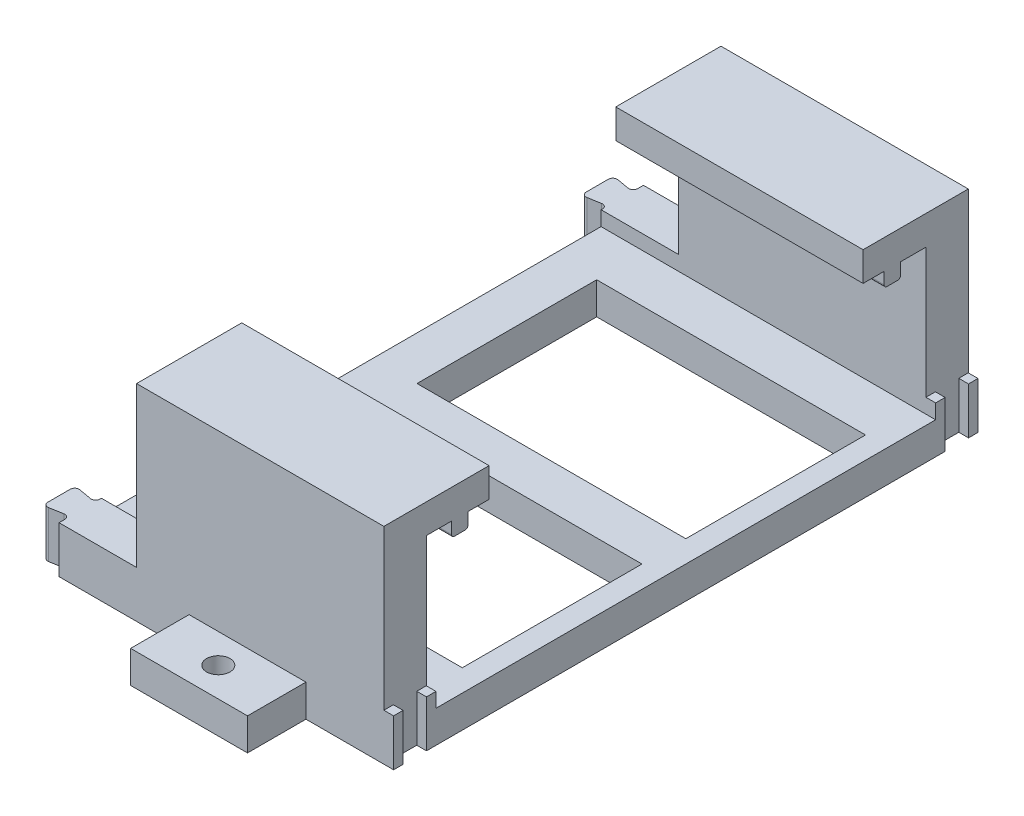
SolidWorks part; units mm, degrees
ref_plane "Front Plane" through (0, 0, 0) normal (0, 0, 1) x (1, 0, 0)
ref_plane "Top Plane" through (0, 0, 0) normal (0, 1, 0) x (1, 0, 0)
ref_plane "Right Plane" through (0, 0, 0) normal (1, 0, 0) x (0, 0, -1)
sketch "Sketch1" plane through (0, 0, 0) normal (0, 1, 0) x (1, 0, 0)
  line L1 (-184.5, -100) -> (184.5, -100)
  line L2 (-184.5, -100) -> (-184.5, 100)
  line L3 (-184.5, 100) -> (184.5, 100)
  line L4 (184.5, -100) -> (184.5, 100)
  line L5 (-184.5, -100) -> (184.5, 100) construction
  line L6 (-184.5, 100) -> (184.5, -100) construction
  point P0 (0, 0)
  dimension "D1" = 200
  dimension "353" = 369
extrude "Boss-Extrude1" add sketch "Sketch1" along normal blind 16
sketch "Sketch2" plane through (0, 16, 0) normal (0, 1, 0) x (1, 0, 0)
  line L0 (-184.5, -100) -> (184.5, -100) construction
  line L1 (-184.5, -100) -> (-155.6166, -100)
  line L2 (-184.5, -100) -> (-184.5, -36.5)
  line L3 (-184.5, -36.5) -> (-169.5, -36.5)
  line L4 (-169.5, -84) -> (-169.5, -36.5)
  line L5 (-184.5, 100) -> (-155.6166, 100)
  line L6 (-184.5, 100) -> (-184.5, 36.5)
  line L7 (-184.5, 36.5) -> (-169.5, 36.5)
  line L8 (-169.5, 84) -> (-169.5, 36.5)
  line L9 (-155.6166, 100) -> (-119.5, 100)
  line L11 (-169.5, 84) -> (-119.5, 84)
  line L12 (-119.5, 100) -> (-119.5, 84)
  line L13 (-155.6166, -100) -> (-119.5, -100)
  line L15 (-169.5, -84) -> (-119.5, -84)
  line L16 (-119.5, -100) -> (-119.5, -84)
  line L17 (-44.5, -100) -> (84.5, -100)
  line L18 (-44.5, -100) -> (-44.5, -84)
  line L19 (-44.5, -84) -> (84.5, -84)
  line L20 (84.5, -100) -> (84.5, -84)
  line L22 (-44.5, 100) -> (84.5, 100)
  line L23 (-44.5, 100) -> (-44.5, 84)
  line L24 (-44.5, 84) -> (84.5, 84)
  line L25 (84.5, 100) -> (84.5, 84)
  line L26 (184.5, -100) -> (184.5, 100) construction
  line L27 (184.5, 100) -> (-184.5, 100) construction
  point P28 (84.5, -92)
  dimension "D1" = 65
  dimension "D2" = 15
  dimension "D3" = 65
  dimension "D4" = 15
  dimension "D5" = 16
  dimension "D6" = 50
  dimension "D7" = 50
  dimension "D8" = 16
  dimension "D9" = 75
  dimension "D10" = 100
extrude "Boss-Extrude2" add sketch "Sketch2" along normal blind 12
sketch "Sketch3" plane through (0, 16, 0) normal (0, 1, 0) x (1, 0, 0)
  line L0 (-119.5, -84) -> (-169.5, -84) construction
  line L1 (-169.5, 84) -> (172.5, 84)
  line L2 (-169.5, 84) -> (-169.5, -84)
  line L3 (-169.5, -84) -> (172.5, -84)
  line L4 (172.5, 84) -> (172.5, -84)
  dimension "D1" = 342
extrude "Cut-Extrude1" cut sketch "Sketch3" against normal blind 5
sketch "Sketch4" plane through (0, 0, -100) normal (0, 0, -1) x (-1, 0, 0)
  line L0 (-84.5, 28) -> (44.5, 28) construction
  line L1 (-69.5, 16) -> (30.5, 16)
  line L2 (-69.5, 16) -> (-69.5, 28)
  line L3 (-69.5, 28) -> (30.5, 28)
  line L4 (30.5, 16) -> (30.5, 28)
  line L5 (-69.5, 16) -> (30.5, 28) construction
  line L6 (-69.5, 28) -> (30.5, 16) construction
  line L8 (-84.5, 28) -> (-84.5, 16) construction
  point P0 (-19.5, 22)
  dimension "D1" = 100
  dimension "D2" = 15
extrude "Boss-Extrude3" add sketch "Sketch4" along normal blind 60
sketch "Sketch8" plane through (0, 28, 0) normal (0, 1, 0) x (1, 0, 0)
  line L0 (-184.5, 36.5) -> (-169.5, 36.5)
  line L1 (-169.5, 36.5) -> (-169.5, 84)
  line L2 (-169.5, 84) -> (-119.5, 84)
  line L3 (-119.5, 84) -> (-119.5, 100)
  line L4 (-119.5, 100) -> (-184.5, 100)
  line L5 (-184.5, 100) -> (-184.5, 36.5)
extrude "Boss-Extrude5" add sketch "Sketch8" along normal blind 42
sketch "Sketch9" plane through (0, 70, 0) normal (0, 1, 0) x (1, 0, 0)
  line L0 (-119.5, 84) -> (-119.5, 70)
  line L1 (-119.5, 70) -> (-155.5, 70)
  line L2 (-155.5, 70) -> (-155.5, 35)
  line L3 (-155.5, 35) -> (-169.5, 35)
  line L4 (-169.5, 36.5) -> (-169.5, 84) construction
  line L5 (-169.5, 84) -> (-169.5, -84) construction
  line L6 (172.5, 84) -> (-169.5, 84) construction
  dimension "D1" = 14
  dimension "D2" = 14
extrude "Extrude-Thin1" add sketch "Sketch9" against normal blind 7 thin thin type one direction wall 10
sketch "Sketch11" plane through (0, 70, 0) normal (0, 1, 0) x (1, 0, 0)
  line L1 (-184.5, 100) -> (-44.5, 100)
  line L2 (-184.5, 100) -> (-184.5, -100)
  line L3 (-184.5, -100) -> (-44.5, -100)
  line L4 (-44.5, 100) -> (-44.5, -100)
extrude "Cut-Extrude5" cut sketch "Sketch11" against normal through all
sketch "Sketch13" plane through (0, 28, 0) normal (0, 1, 0) x (1, 0, 0)
  line L0 (-44.5, 96.22) -> (-44.5, 87.78)
  line L1 (-44.5, 100) -> (-44.5, 84) construction
  line L2 (-44.5, 87.78) -> (-52.3, 86.4046)
  line L3 (-52.3, 86.4046) -> (-52.3, 97.5954)
  line L4 (-52.3, 97.5954) -> (-44.5, 96.22)
  line L5 (-44.5, -87.78) -> (-44.5, -96.22)
  line L6 (-44.5, -96.22) -> (-52.5, -97.6306)
  line L7 (-52.5, -97.6306) -> (-52.5, -86.3694)
  line L8 (-52.5, -86.3694) -> (-44.5, -87.78)
  line L9 (-44.5, -84) -> (-44.5, -100) construction
  dimension "D1" = 3.78
  dimension "D2" = 3.78
  dimension "D3" = 7.8
  dimension "D4" = 80
  dimension "D5" = 80
  dimension "D6" = 3.78
  dimension "D7" = 3.78
  dimension "D8" = 80
  dimension "D9" = 8
  dimension "D10" = 80
extrude "Boss-Extrude6" add sketch "Sketch13" against normal through all
fillet "Fillet1" radius 1.5 8 edges at (-44.5, 14, 87.78) (-52.5, 14, 86.3694) (-52.5, 14, 97.6306) (-44.5, 14, 96.22) (-44.5, 14, -96.22) (-44.5, 14, -87.78) (-52.3, 14, -86.4046) (-52.3, 14, -97.5954)
sketch "Sketch14" plane through (0, 0, 0) normal (0, 0, 1) x (1, 0, 0)
  line L0 (84.5, 16) -> (184.5, 16) construction
  line L1 (84.5, 28) -> (-67.1004, 28)
  line L2 (84.5, 28) -> (84.5, 16)
  line L3 (84.5, 16) -> (-67.1004, 16)
  line L4 (-67.1004, 28) -> (-67.1004, 16)
extrude "Cut-Extrude6" cut sketch "Sketch14" along normal through all and the other way through all
sketch "Sketch15" plane through (0, 16, 0) normal (0, 1, 0) x (1, 0, 0)
  line L0 (184.5, 100) -> (-44.5, 100) construction
  line L1 (-17.9669, 100) -> (79.8991, 100)
  line L2 (-17.9669, 100) -> (-17.9669, 84)
  line L3 (-17.9669, 84) -> (79.8991, 84)
  line L4 (79.8991, 100) -> (79.8991, 84)
  line L5 (172.5, 84) -> (-44.5, 84) construction
extrude "Boss-Extrude7" add sketch "Sketch15" along normal blind 62
sketch "Sketch16" plane through (0, 0, -84) normal (0, 0, 1) x (1, 0, 0)
  line L0 (79.8991, 78) -> (79.8991, 16) construction
  line L1 (-17.9669, 78) -> (79.8991, 78)
  line L2 (-17.9669, 78) -> (-17.9669, 60.5)
  line L3 (-17.9669, 60.5) -> (79.8991, 60.5)
  line L4 (79.8991, 78) -> (79.8991, 60.5)
  line L5 (172.5, 11) -> (-44.5, 11) construction
  dimension "D1" = 49.5
extrude "Boss-Extrude8" add sketch "Sketch16" along normal blind 20
sketch "Sketch17" plane through (0, 60.5, 0) normal (0, -1, 0) x (1, 0, 0)
  line L0 (-17.9669, -64) -> (-17.9669, -84) construction
  line L1 (-17.9669, -71.2) -> (79.8991, -71.2)
  line L2 (-17.9669, -71.2) -> (-17.9669, -76.85)
  line L3 (-17.9669, -76.85) -> (79.8991, -76.85)
  line L4 (79.8991, -71.2) -> (79.8991, -76.85)
  line L5 (79.8991, -64) -> (79.8991, -84) construction
  line L6 (-17.9669, -84) -> (79.8991, -84) construction
  dimension "D1" = 5.65
  dimension "D2" = 7.15
extrude "Boss-Extrude9" add sketch "Sketch17" along normal blind 5
fillet "Fillet3" radius 1 2 edges at (30.9661, 55.5, -76.85) (30.9661, 55.5, -71.2)
sketch "Sketch18" plane through (0, 16, 0) normal (0, 1, 0) x (1, 0, 0)
  line L0 (184.5, -100) -> (184.5, 100) construction
  line L1 (172.5, 84) -> (184.5, 84)
  line L2 (172.5, 84) -> (172.5, -84)
  line L3 (172.5, -84) -> (184.5, -84)
  line L4 (184.5, 84) -> (184.5, -84)
  line L5 (-44.5, -84) -> (172.5, -84) construction
extrude "Cut-Extrude7" cut sketch "Sketch18" against normal blind 5
sketch "Sketch19" plane through (0, 0, -100) normal (0, 0, -1) x (-1, 0, 0)
  line L1 (0, 0) -> (-40, 0)
  line L2 (0, 0) -> (0, 11)
  line L3 (0, 11) -> (-40, 11)
  line L4 (-40, 0) -> (-40, 11)
  line L5 (-184.5, 0) -> (-144.5, 0)
  line L6 (-184.5, 0) -> (-184.5, 11)
  line L7 (-184.5, 11) -> (-144.5, 11)
  line L8 (-144.5, 0) -> (-144.5, 11)
  dimension "D1" = 11
  dimension "D2" = 11
  dimension "D3" = 40
  dimension "D4" = 40
extrude "Boss-Extrude10" add sketch "Sketch19" along normal blind 20
sketch "Sketch20" plane through (0, 11, 0) normal (0, 1, 0) x (1, 0, 0)
  line L0 (40, 120) -> (40, 100) construction
  line L1 (0, 120) -> (40, 120) construction
  line L2 (144.5, 120) -> (184.5, 120) construction
  line L3 (184.5, 120) -> (184.5, 100) construction
  circle A0 centre (164.5, 110) radius 4
  circle A1 centre (20, 110) radius 4
  dimension "D1" = 20
  dimension "D2" = 10
  dimension "D3" = 10
  dimension "D4" = 20
extrude "Cut-Extrude8" cut sketch "Sketch20" against normal through all
mirror "Mirror3" about plane through (0, 0, 0) normal (0, 0, 1) of "Cut-Extrude8", "Boss-Extrude10", "Boss-Extrude9", "Boss-Extrude7", "Boss-Extrude8", "Fillet3"
sketch "Sketch21" plane through (0, 11, 0) normal (0, 1, 0) x (1, 0, 0)
  line L1 (-29.5, 7.5) -> (62.5, 7.5)
  line L2 (-29.5, 7.5) -> (-29.5, 69)
  line L3 (-29.5, 69) -> (62.5, 69)
  line L4 (62.5, 7.5) -> (62.5, 69)
  line L5 (77.5, 69) -> (169.5, 69)
  line L6 (77.5, 69) -> (77.5, 7.5)
  line L7 (77.5, 7.5) -> (169.5, 7.5)
  line L8 (169.5, 69) -> (169.5, 7.5)
  line L9 (-44.5, -84) -> (-44.5, 84) construction
  line L10 (62.5, -7.5) -> (-29.5, -7.5)
  line L11 (62.5, -7.5) -> (62.5, -69)
  line L12 (62.5, -69) -> (-29.5, -69)
  line L13 (-29.5, -7.5) -> (-29.5, -69)
  line L14 (77.5, -7.5) -> (169.5, -7.5)
  line L15 (77.5, -7.5) -> (77.5, -69)
  line L16 (77.5, -69) -> (169.5, -69)
  line L17 (169.5, -7.5) -> (169.5, -69)
  line L18 (184.5, -84) -> (184.5, 84) construction
  line L19 (-44.5, -84) -> (184.5, -84) construction
  line L20 (184.5, 84) -> (79.8991, 84) construction
  line L21 (-17.9669, 84) -> (-44.5, 84) construction
  line L22 (-42.9, 0) -> (42.9, 0) construction
  dimension "D1" = 15
  dimension "D2" = 15
  dimension "D3" = 15
  dimension "D4" = 15
  dimension "D5" = 15
  dimension "D6" = 15
  dimension "D7" = 15
  dimension "D8" = 15
  dimension "D9" = 7.5
  dimension "D10" = 7.5
  dimension "D11" = 7.5
  dimension "D12" = 7.5
  dimension "D13" = 122
  dimension "D14" = 15
extrude "Cut-Extrude9" cut sketch "Sketch21" against normal through all
sketch "Sketch22" plane through (79.8991, 0, 0) normal (1, 0, 0) x (0, 0, -1)
  line L0 (-84, 11) -> (84, 11) construction
  line L1 (-84, 60.5) -> (-85.5, 60.5)
  line L2 (-84, 60.5) -> (-84, 11)
  line L3 (-84, 11) -> (-85.5, 11)
  line L4 (-85.5, 60.5) -> (-85.5, 11)
  dimension "D1" = 1.5
extrude "Cut-Extrude10" cut sketch "Sketch22" against normal through all both and the other way through all
mirror "Mirror4" about plane through (0, 0, 0) normal (0, 0, 1) of "Cut-Extrude10"
sketch "Sketch23" plane through (0, 78, 0) normal (0, 1, 0) x (1, 0, 0)
  line L0 (79.8991, -100) -> (-17.9669, -100) construction
  line L1 (79.8991, -64) -> (66.6759, -64)
  line L2 (79.8991, -64) -> (79.8991, -100)
  line L3 (79.8991, -100) -> (66.6759, -100)
  line L4 (66.6759, -64) -> (66.6759, -100)
extrude "Cut-Extrude11" cut sketch "Sketch23" against normal up to surface (62 mm away) up to face at (-42.7445, 16, 92.25)
mirror "Mirror5" about plane through (0, 0, 0) normal (0, 0, 1) of "Cut-Extrude11"
sketch "Sketch25" plane through (0, 0, 0) normal (0, 1, 0) x (1, 0, 0)
  line L1 (184.5, -120) -> (70, -120)
  line L2 (184.5, -120) -> (184.5, 120)
  line L3 (184.5, 120) -> (70, 120)
  line L4 (70, -120) -> (70, 120)
  line L5 (77.5, 69) -> (77.5, 7.5) construction
  line L6 (144.5, 120) -> (184.5, 120) construction
  dimension "D1" = 7.5
extrude "Cut-Extrude12" cut sketch "Sketch25" along normal up to surface (16 mm away) up to face at (-42.7445, 16, 92.25)
sketch "Sketch26" plane through (0, 0, -64) normal (0, 0, 1) x (1, 0, 0)
  line L0 (-17.9669, 78) -> (-17.9669, 16) construction
  line L1 (66.6759, 78) -> (-17.9669, 78)
  line L2 (66.6759, 78) -> (66.6759, 70.5)
  line L3 (66.6759, 70.5) -> (-17.9669, 70.5)
  line L4 (-17.9669, 78) -> (-17.9669, 70.5)
  line L5 (-17.9669, 60.5) -> (66.6759, 60.5) construction
  dimension "D1" = 10
extrude "Cut-Extrude13" cut sketch "Sketch26" against normal through all both and the other way through all
sketch "Sketch28" plane through (0, 16, 0) normal (0, 1, 0) x (1, 0, 0)
  line L0 (70, -100) -> (70, -85.5) construction
  line L1 (70, -88.75) -> (66.6759, -88.75)
  line L2 (70, -88.75) -> (70, -96.75)
  line L3 (70, -96.75) -> (66.6759, -96.75)
  line L4 (66.6759, -88.75) -> (66.6759, -96.75)
  line L5 (66.6759, -85.5) -> (66.6759, -100) construction
  line L6 (70, -85.5) -> (66.6759, -85.5) construction
  dimension "D1" = 8
  dimension "D2" = 3.25
extrude "Cut-Extrude14" cut sketch "Sketch28" against normal through all
mirror "Mirror6" about plane through (0, 0, 0) normal (0, 0, 1) of "Cut-Extrude14"
equation "\"´7.25\"=7.35"
